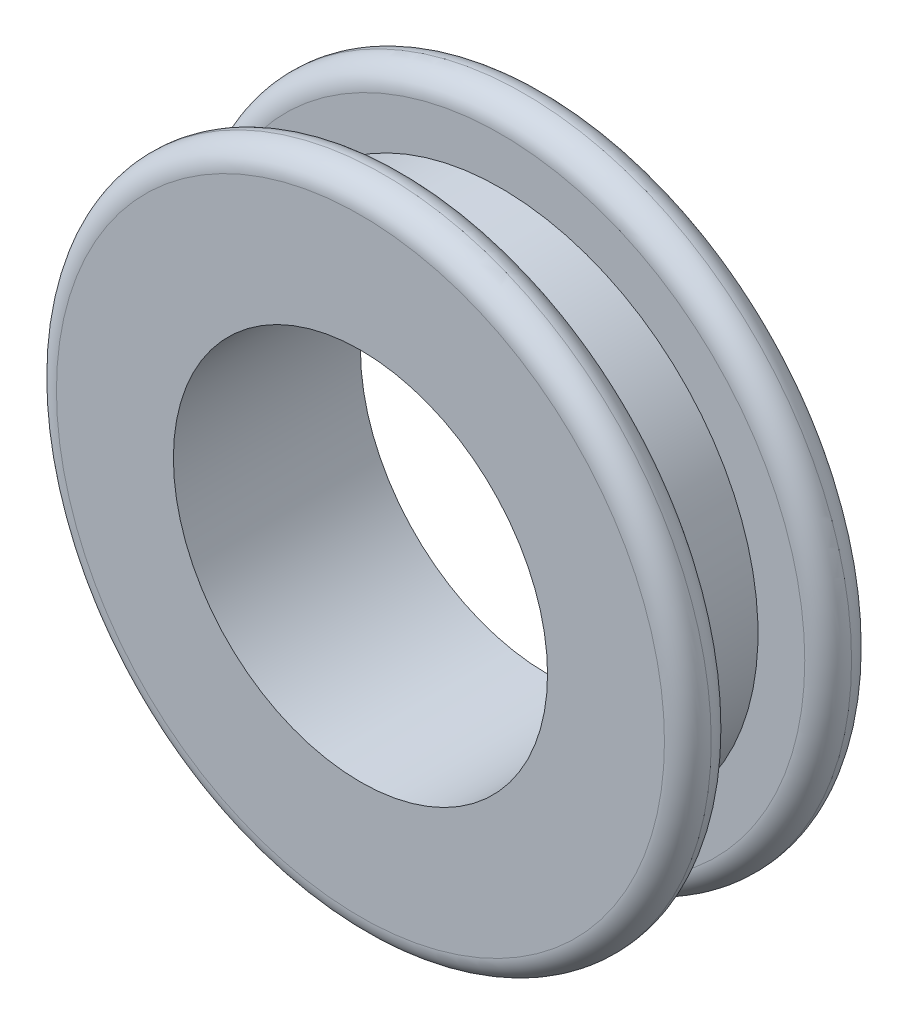
SolidWorks part; units mm, degrees
material "6061 合金"
ref_plane "前视基准面" through (0, 0, 0) normal (0, 0, 1) x (1, 0, 0)
ref_plane "上视基准面" through (0, 0, 0) normal (0, 1, 0) x (1, 0, 0)
ref_plane "右视基准面" through (0, 0, 0) normal (1, 0, 0) x (0, 0, -1)
sketch "草图1" plane through (0, 0, 0) normal (0, 0, 1) x (1, 0, 0)
  circle A0 centre (0, 0) radius 4
  circle A1 centre (0, 0) radius 7
  dimension "D1" = 8
  dimension "D2" = 14
extrude "凸台-拉伸1" add sketch "草图1" along normal blind 4
sketch "草图2" plane through (0, 0, 0) normal (1, 0, 0) x (0, 0, -1)
  line L0 (1.5109, 0) -> (-6.253, 0) construction
  line L2 (-4, 7) -> (-4, -7) construction
  line L3 (-3, 7) -> (-1, 7)
  line L4 (-3, 7) -> (-3, 5.5)
  line L5 (-3, 5.5) -> (-1, 5.5)
  line L6 (-1, 7) -> (-1, 5.5)
  dimension "D1" = 1
  dimension "D2" = 2
  dimension "D3" = 1.5
  dimension "D4" = 5.5
revolve "切除-旋转1" cut sketch "草图2" angle 360 about L0
fillet "圆角1" radius 0.5 4 edges at (-7, 0, 1) (7, 0, 0) (7, 0, 4) (-7, 0, 3)
